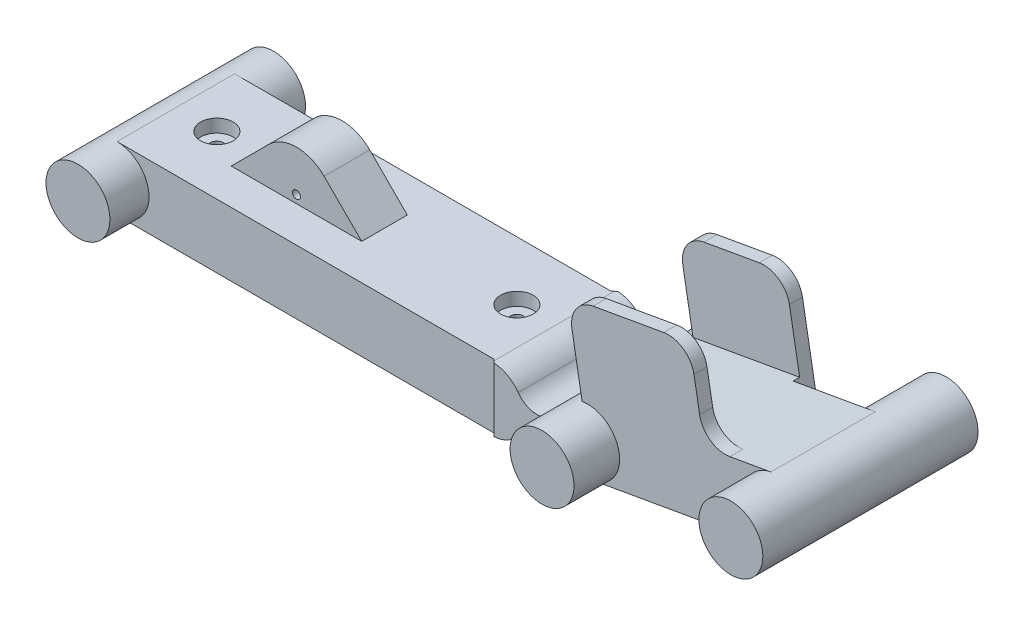
SolidWorks part; units mm, degrees
ref_plane "前视基准面" through (0, 0, 0) normal (0, 0, 1) x (1, 0, 0)
ref_plane "上视基准面" through (0, 0, 0) normal (0, 1, 0) x (1, 0, 0)
ref_plane "右视基准面" through (0, 0, 0) normal (1, 0, 0) x (0, 0, -1)
sketch "草图1" plane through (0, 0, 0) normal (0, 0, 1) x (1, 0, 0)
  line L0 (0, 0) -> (31.45, 0) construction
  line L1 (0, 2.45) -> (29, 2.45)
  line L3 (0, -2.45) -> (29, -2.45)
  line L5 (31.45, 0) -> (60.6363, 5.1463) construction
  line L6 (35.8994, 3.2723) -> (50.376, 5.825)
  line L7 (36.7502, -1.5532) -> (51.2269, 0.9994)
  arc A0 (0, 2.45) -> (0, -2.45) centre (0, 0) ccw
  arc A1 (29, -2.45) -> (31.1036, -1.2559) centre (29, 0) ccw
  arc A2 (34.5691, -0.8493) -> (36.7502, -1.5532) centre (36.3248, 0.8596) ccw
  arc A3 (51.2269, 0.9994) -> (50.376, 5.825) centre (50.8015, 3.4122) ccw
  arc A4 (30.9997, 1.4155) -> (34.0517, 1.7737) centre (32.4281, 2.4266) ccw
  arc A5 (34.5691, -0.8493) -> (31.1036, -1.2559) centre (32.9926, -2.3837) ccw
  arc A6 (30.9997, 1.4155) -> (29, 2.45) centre (29, 0) ccw
  arc A7 (35.8994, 3.2723) -> (34.0517, 1.7737) centre (36.3248, 0.8596) ccw
  dimension "D1" = 29
  dimension "D3" = 170
  dimension "D4" = 4.95
  dimension "D5" = 14.7
  dimension "D6" = 4.9
  dimension "D7" = 4.9
  dimension "D8" = 3.5
  dimension "D2" = 4.9
extrude "凸台-拉伸1" add sketch "草图1" along normal mid plane 9
sketch "草图2" plane through (0, 0, 0) normal (0, 0, 1) x (1, 0, 0)
  line L0 (6, 2.45) -> (11, 7.45)
  line L1 (29, 2.45) -> (0, 2.45) construction
  line L2 (11, 7.45) -> (16, 2.45)
  line L3 (11, 7.45) -> (11, 2.45) construction
  line L4 (6, 2.45) -> (16, 2.45)
  circle A0 centre (11, 3.05) radius 0.3
  dimension "D5" = 0.6
  dimension "D1" = 45
  dimension "D2" = 10
  dimension "D3" = 45
  dimension "D4" = 6
extrude "凸台-拉伸2" add sketch "草图2" along normal mid plane 3.5
fillet "圆角1" radius 3 1 edges at (11, 7.45, 0)
sketch "草图3" plane through (0, 0, 4.5) normal (0, 0, 1) x (1, 0, 0)
  circle A0 centre (0, 0) radius 2.45
extrude "凸台-拉伸3" add sketch "草图3" along normal blind 3
sketch "草图4" plane through (0, 0, -4.5) normal (0, 0, -1) x (-1, 0, 0)
  circle A0 centre (0, 0) radius 2.45
extrude "凸台-拉伸4" add sketch "草图4" along normal blind 3
sketch "草图5" plane through (0, 0, -4.5) normal (0, 0, -1) x (-1, 0, 0)
  line L0 (-29, 2.45) -> (-29, -2.45)
  line L4 (0, 2.45) -> (-29, 2.45)
  line L5 (-35.8994, 3.2723) -> (-50.376, 5.825)
  line L6 (-51.2269, 0.9994) -> (-36.7502, -1.5532)
  line L7 (-29, -2.45) -> (0, -2.45)
  line L9 (-35.8994, 3.2723) -> (-50.376, 5.825)
  line L10 (-51.2269, 0.9994) -> (-36.7502, -1.5532)
  arc A8 (0, 2.45) -> (0, -2.45) centre (0, 0) ccw
  arc A9 (-29, 2.45) -> (-30.9997, 1.4155) centre (-29, 0) ccw
  arc A10 (-34.0517, 1.7737) -> (-30.9997, 1.4155) centre (-32.4281, 2.4266) ccw
  arc A11 (-34.0517, 1.7737) -> (-35.8994, 3.2723) centre (-36.3248, 0.8596) ccw
  arc A12 (-50.376, 5.825) -> (-51.2269, 0.9994) centre (-50.8015, 3.4122) ccw
  arc A13 (-36.7502, -1.5532) -> (-34.5691, -0.8493) centre (-36.3248, 0.8596) ccw
  arc A14 (-31.1036, -1.2559) -> (-34.5691, -0.8493) centre (-32.9926, -2.3837) ccw
  arc A15 (-31.1036, -1.2559) -> (-29, -2.45) centre (-29, 0) ccw
  arc A17 (-29, 2.45) -> (-30.9997, 1.4155) centre (-29, 0) ccw
  arc A18 (-34.0517, 1.7737) -> (-30.9997, 1.4155) centre (-32.4281, 2.4266) ccw
  arc A19 (-34.0517, 1.7737) -> (-35.8994, 3.2723) centre (-36.3248, 0.8596) ccw
  arc A20 (-50.376, 5.825) -> (-51.2269, 0.9994) centre (-50.8015, 3.4122) ccw
  arc A21 (-36.7502, -1.5532) -> (-34.5691, -0.8493) centre (-36.3248, 0.8596) ccw
  arc A22 (-31.1036, -1.2559) -> (-34.5691, -0.8493) centre (-32.9926, -2.3837) ccw
  arc A23 (-31.1036, -1.2559) -> (-29, -2.45) centre (-29, 0) ccw
  dimension "D1" = 0
extrude "凸台-拉伸5" add sketch "草图5" along normal blind 0.25 contours L0 A23 A22 A21 L10 A20 L9 A19 A18 A17
sketch "草图6" plane through (0, 0, 4.5) normal (0, 0, 1) x (1, 0, 0)
  line L0 (29, -2.45) -> (29, 2.45)
  line L4 (0, -2.45) -> (29, -2.45)
  line L5 (36.7502, -1.5532) -> (51.2269, 0.9994)
  line L6 (50.376, 5.825) -> (35.8994, 3.2723)
  line L7 (29, 2.45) -> (0, 2.45)
  line L9 (36.7502, -1.5532) -> (51.2269, 0.9994)
  line L10 (50.376, 5.825) -> (35.8994, 3.2723)
  arc A8 (0, -2.45) -> (0, 2.45) centre (0, 0) ccw
  arc A9 (29, -2.45) -> (31.1036, -1.2559) centre (29, 0) ccw
  arc A10 (34.5691, -0.8493) -> (31.1036, -1.2559) centre (32.9926, -2.3837) ccw
  arc A11 (34.5691, -0.8493) -> (36.7502, -1.5532) centre (36.3248, 0.8596) ccw
  arc A12 (51.2269, 0.9994) -> (50.376, 5.825) centre (50.8015, 3.4122) ccw
  arc A13 (35.8994, 3.2723) -> (34.0517, 1.7737) centre (36.3248, 0.8596) ccw
  arc A14 (30.9997, 1.4155) -> (34.0517, 1.7737) centre (32.4281, 2.4266) ccw
  arc A15 (30.9997, 1.4155) -> (29, 2.45) centre (29, 0) ccw
  arc A17 (29, -2.45) -> (31.1036, -1.2559) centre (29, 0) ccw
  arc A18 (34.5691, -0.8493) -> (31.1036, -1.2559) centre (32.9926, -2.3837) ccw
  arc A19 (34.5691, -0.8493) -> (36.7502, -1.5532) centre (36.3248, 0.8596) ccw
  arc A20 (51.2269, 0.9994) -> (50.376, 5.825) centre (50.8015, 3.4122) ccw
  arc A21 (35.8994, 3.2723) -> (34.0517, 1.7737) centre (36.3248, 0.8596) ccw
  arc A22 (30.9997, 1.4155) -> (34.0517, 1.7737) centre (32.4281, 2.4266) ccw
  arc A23 (30.9997, 1.4155) -> (29, 2.45) centre (29, 0) ccw
  dimension "D1" = 0
extrude "凸台-拉伸6" add sketch "草图6" along normal blind 0.25
sketch "草图7" plane through (0, 0, -4.75) normal (0, 0, -1) x (-1, 0, 0)
  circle A0 centre (-36.3248, 0.8596) radius 2.45
  circle A1 centre (-50.8015, 3.4122) radius 2.45
extrude "凸台-拉伸7" add sketch "草图7" along normal blind 3.5
sketch "草图8" plane through (0, 0, 4.75) normal (0, 0, 1) x (1, 0, 0)
  circle A0 centre (50.8015, 3.4122) radius 2.45
  circle A1 centre (36.3248, 0.8596) radius 2.45
extrude "凸台-拉伸8" add sketch "草图8" along normal blind 3.5
sketch "草图9" plane through (0, 0, 4.75) normal (0, 0, 1) x (1, 0, 0)
  line L0 (35.8994, 3.2723) -> (45.255, 4.922)
  line L1 (35.8994, 3.2723) -> (34.7706, 9.6736)
  line L2 (45.255, 4.922) -> (44.1263, 11.3232)
  line L3 (34.7706, 9.6736) -> (44.1263, 11.3232)
  dimension "D1" = 9.5
  dimension "D2" = 6.5
extrude "凸台-拉伸9" add sketch "草图9" against normal blind 1
fillet "圆角4" radius 2 1 edges at (45.255, 4.922, 4.25)
fillet "圆角5" radius 2 2 edges at (34.7706, 9.6736, 4.25) (44.1263, 11.3232, 4.25)
sketch "草图10" plane through (0, 0, -4.75) normal (0, 0, -1) x (-1, 0, 0)
  line L0 (-35.8994, 3.2723) -> (-44.0733, 4.7136)
  line L1 (-35.8994, 3.2723) -> (-34.7706, 9.6736)
  line L2 (-44.0733, 4.7136) -> (-42.9446, 11.1149)
  line L3 (-34.7706, 9.6736) -> (-42.9446, 11.1149)
  line L4 (-35.8994, 3.2723) -> (-47.2246, 5.2693) construction
  dimension "D1" = 6.5
  dimension "D2" = 8.3
extrude "凸台-拉伸10" add sketch "草图10" against normal blind 1
fillet "圆角6" radius 2 2 edges at (34.7706, 9.6736, -4.25) (42.9446, 11.1149, -4.25)
sketch "草图12" plane through (0, 0, -4.75) normal (0, 0, -1) x (-1, 0, 0)
  line L0 (-44.0733, 4.7136) -> (-44.9241, -0.1119)
  line L5 (-35.8994, 3.2723) -> (-35.1179, 7.704)
  line L6 (-36.7403, 10.0209) -> (-40.9749, 10.7676)
  line L7 (-43.2918, 9.1453) -> (-44.0733, 4.7136)
  line L8 (-44.0733, 4.7136) -> (-50.376, 5.825)
  line L9 (-51.2269, 0.9994) -> (-36.7502, -1.5532)
  line L13 (-44.0733, 4.7136) -> (-50.376, 5.825)
  line L14 (-51.2269, 0.9994) -> (-44.9241, -0.1119)
  arc A4 (-35.1179, 7.704) -> (-36.7403, 10.0209) centre (-37.0876, 8.0513) ccw
  arc A5 (-40.9749, 10.7676) -> (-43.2918, 9.1453) centre (-41.3222, 8.798) ccw
  arc A6 (-51.2269, 0.9994) -> (-50.376, 5.825) centre (-50.8015, 3.4122) ccw
  arc A7 (-35.8994, 3.2723) -> (-36.7502, -1.5532) centre (-36.3248, 0.8596) ccw
  arc A10 (-51.2269, 0.9994) -> (-50.376, 5.825) centre (-50.8015, 3.4122) ccw
  dimension "D1" = 0
extrude "切除-拉伸1" cut sketch "草图12" against normal blind 1.5
fillet "圆角7" radius 2 1 edges at (44.9241, -0.1119, -4)
chamfer "倒角1" distance 0.125 angle 45 2 edges at (29, 0, -4.75) (29, 0, -4.5)
chamfer "倒角2" distance 0.125 angle 45 2 edges at (29, 0, 4.75) (29, 0, 4.5)
sketch "草图13" plane through (0, 2.45, 0) normal (0, 1, 0) x (1, 0, 0)
  line L0 (0, -4.5) -> (0, 4.5) construction
  circle A0 centre (3.15, 0) radius 1.25
  circle A1 centre (26.15, 0) radius 1.25
  dimension "D1" = 23
  dimension "D2" = 3.15
extrude "切除-拉伸2" cut sketch "草图13" against normal blind 1
sketch "草图14" plane through (0, 1.45, 0) normal (0, 1, 0) x (1, 0, 0)
  circle A0 centre (3.15, 0) radius 0.5
  circle A1 centre (26.15, 0) radius 0.5
extrude "切除-拉伸3" cut sketch "草图14" against normal up to next
sketch "草图15" plane through (0, -2.45, 0) normal (0, -1, 0) x (1, 0, 0)
  circle A0 centre (3.15, 0) radius 1.25
  circle A1 centre (26.15, 0) radius 1.25
extrude "切除-拉伸4" cut sketch "草图15" against normal blind 1
